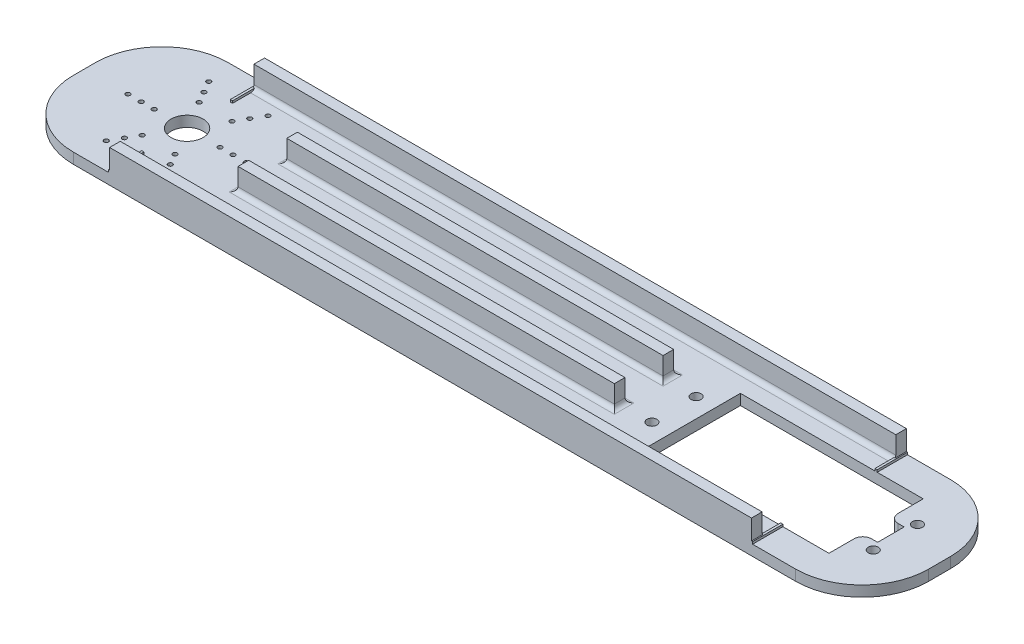
SolidWorks part; units mm, degrees
ref_plane "Front Plane" through (0, 0, 0) normal (0, 0, 1) x (1, 0, 0)
ref_plane "Top Plane" through (0, 0, 0) normal (0, 1, 0) x (1, 0, 0)
ref_plane "Right Plane" through (0, 0, 0) normal (1, 0, 0) x (0, 0, -1)
sketch "Sketch1" plane through (0, 0, 0) normal (0, 1, 0) x (1, 0, 0)
  line L1 (-65.6771, 38.9958) -> (127.5229, 38.9958)
  line L2 (-65.6771, 38.9958) -> (-65.6771, 3.9958)
  line L3 (-65.6771, 3.9958) -> (127.5229, 3.9958)
  line L4 (127.5229, 38.9958) -> (127.5229, 3.9958)
  dimension "D1" = 193.2
  dimension "D2" = 35
extrude "Boss-Extrude1" add sketch "Sketch1" along normal blind 2.4
sketch "Sketch2" plane through (0, 2.4, 0) normal (0, 1, 0) x (1, 0, 0)
  line L0 (-42.4771, 38.9958) -> (-42.4771, 2.4158) construction
  line L1 (127.5229, 38.9958) -> (-65.6771, 38.9958) construction
  line L2 (-65.6771, 21.4958) -> (127.5229, 21.4958) construction
  line L3 (-65.6771, 38.9958) -> (-65.6771, 3.9958) construction
  line L4 (127.5229, 3.9958) -> (127.5229, 38.9958) construction
  line L5 (112.5229, 38.9958) -> (112.5229, 3.9958) construction
  line L6 (-65.6771, 3.9958) -> (127.5229, 3.9958) construction
  line L7 (72.5229, 38.9958) -> (72.5229, 3.9958) construction
  line L9 (72.5229, 31.4958) -> (112.5229, 31.4958)
  line L10 (72.5229, 31.4958) -> (72.5229, 11.4958)
  line L11 (72.5229, 11.4958) -> (112.5229, 11.4958)
  line L12 (112.5229, 31.4958) -> (112.5229, 11.4958)
  circle A0 centre (67.5229, 26.4958) radius 1.13
  circle A1 centre (117.5229, 26.4958) radius 1.13
  circle A2 centre (117.5229, 16.4958) radius 1.13
  circle A3 centre (67.5229, 16.4958) radius 1.13
  circle A4 centre (-42.4771, 21.4958) radius 3.625
  circle A5 centre (-49.9071, 21.4958) radius 0.5
  circle A6 centre (-52.8421, 21.4958) radius 0.5
  circle A7 centre (-55.8471, 21.4958) radius 0.5
  circle A8 centre (-49.1621, 33.0745) radius 0.5
  circle A9 centre (-47.6596, 30.4721) radius 0.5
  circle A10 centre (-46.1921, 27.9303) radius 0.5
  circle A11 centre (-35.7921, 33.0745) radius 0.5
  circle A12 centre (-37.2946, 30.4721) radius 0.5
  circle A13 centre (-38.7621, 27.9303) radius 0.5
  circle A14 centre (-29.1071, 21.4958) radius 0.5
  circle A15 centre (-32.1121, 21.4958) radius 0.5
  circle A16 centre (-35.0471, 21.4958) radius 0.5
  circle A17 centre (-35.7921, 9.917) radius 0.5
  circle A18 centre (-37.2946, 12.5194) radius 0.5
  circle A19 centre (-38.7621, 15.0612) radius 0.5
  circle A20 centre (-49.1621, 9.917) radius 0.5
  circle A21 centre (-47.6596, 12.5194) radius 0.5
  circle A22 centre (-46.1921, 15.0612) radius 0.5
  point P24 (-42.4771, 21.4958)
  point P70 (-42.4771, 21.4958)
  dimension "D5" = 2.26
  dimension "D6" = 2.26
  dimension "D11" = 7.25
  dimension "D12" = 7.43
  dimension "D13" = 10.365
  dimension "D14" = 13.37
  dimension "D15" = 1
  dimension "D16" = 1
  dimension "D17" = 1
  dimension "D19" = 20
  dimension "D1" = 23.2
  dimension "D2" = 15
  dimension "D3" = 40
  dimension "D4" = 10
  dimension "D7" = 5
  dimension "D8" = 5
  dimension "D9" = 5
  dimension "D10" = 5
  dimension "D18" = 6
extrude "Cut-Extrude1" cut sketch "Sketch2" against normal blind 2.4
sketch "Sketch4" plane through (0, 2.4, 0) normal (0, 1, 0) x (1, 0, 0)
  line L0 (72.5229, 21.4958) -> (127.5229, 21.4958) construction
  line L1 (72.5229, 31.4958) -> (72.5229, 11.4958) construction
  line L2 (127.5229, 3.9958) -> (127.5229, 38.9958) construction
  line L3 (112.5229, 11.4958) -> (112.5229, 31.4958) construction
  line L4 (112.5229, 24.4958) -> (116.5229, 24.4958)
  line L5 (112.5229, 24.4958) -> (112.5229, 18.4958)
  line L6 (112.5229, 18.4958) -> (116.5229, 18.4958)
  line L7 (116.5229, 24.4958) -> (116.5229, 18.4958)
  dimension "D1" = 6
  dimension "D2" = 3
  dimension "D3" = 4
extrude "Cut-Extrude2" cut sketch "Sketch4" against normal blind 2.4
fillet "Fillet1" radius 15 4 edges at (127.5229, 1.2, -38.9958) (127.5229, 1.2, -3.9958) (-65.6771, 1.2, -3.9958) (-65.6771, 1.2, -38.9958)
sketch "Sketch5" plane through (0, 2.4, 0) normal (0, 1, 0) x (1, 0, 0)
  line L0 (-42.4771, 21.4958) -> (127.5229, 21.4958) construction
  line L1 (127.5229, 18.9958) -> (127.5229, 23.9958) construction
  line L2 (-42.4771, 38.9958) -> (-42.4771, 3.9958) construction
  line L3 (112.5229, 38.9958) -> (-50.6771, 38.9958) construction
  line L4 (-50.6771, 3.9958) -> (112.5229, 3.9958) construction
  line L5 (102.5229, 38.9958) -> (102.5229, 3.9958) construction
  line L6 (112.5229, 31.4958) -> (72.5229, 31.4958) construction
  line L7 (102.2729, 38.9958) -> (102.7729, 38.9958)
  line L8 (102.2729, 38.9958) -> (102.2729, 31.4958)
  line L9 (102.2729, 31.4958) -> (102.7729, 31.4958)
  line L10 (102.7729, 38.9958) -> (102.7729, 31.4958)
  line L11 (102.7729, 3.9958) -> (102.7729, 11.4958)
  line L12 (102.2729, 11.4958) -> (102.7729, 11.4958)
  line L13 (102.2729, 3.9958) -> (102.2729, 11.4958)
  line L14 (102.2729, 3.9958) -> (102.7729, 3.9958)
  line L15 (-42.2271, 3.9958) -> (-42.2271, 11.4958)
  line L16 (-42.7271, 38.9958) -> (-42.2271, 38.9958)
  line L17 (-42.7271, 38.9958) -> (-42.7271, 31.4958)
  line L18 (-42.7271, 31.4958) -> (-42.2271, 31.4958)
  line L19 (-42.2271, 38.9958) -> (-42.2271, 31.4958)
  line L20 (-42.7271, 11.4958) -> (-42.2271, 11.4958)
  line L21 (-42.7271, 3.9958) -> (-42.7271, 11.4958)
  line L22 (-42.7271, 3.9958) -> (-42.2271, 3.9958)
  dimension "D1" = 145
  dimension "D2" = 0.5
  dimension "D3" = 0.25
  dimension "D4" = 0.25
  dimension "D5" = 0.5
  dimension "D6" = 7.5
extrude "Boss-Extrude2" add sketch "Sketch5" along normal blind 0.5
sketch "Sketch7" plane through (0, 2.4, 0) normal (0, 1, 0) x (1, 0, 0)
  line L0 (71.8729, 32.1458) -> (71.8729, 10.8458)
  line L1 (72.5229, 31.4958) -> (112.5229, 31.4958)
  line L2 (72.5229, 31.4958) -> (72.5229, 11.4958)
  line L3 (72.5229, 11.4958) -> (112.5229, 11.4958)
  line L4 (112.5229, 31.4958) -> (112.5229, 11.4958)
  line L5 (71.8729, 10.8458) -> (113.1729, 10.8458)
  line L6 (113.1729, 32.1458) -> (113.1729, 10.8458)
  line L7 (71.8729, 32.1458) -> (113.1729, 32.1458)
  dimension "D1" = 0.65
extrude "Cut-Extrude3" cut sketch "Sketch7" against normal through all both and the other way through all
sketch "Sketch8" plane through (0, 2.4, 0) normal (0, 1, 0) x (1, 0, 0)
  line L0 (102.5229, 38.9958) -> (102.5229, 3.9958) construction
  line L1 (-42.4771, 38.9958) -> (102.5229, 38.9958)
  line L2 (-42.4771, 38.9958) -> (-42.4771, 36.5958)
  line L3 (-42.4771, 36.5958) -> (102.5229, 36.5958)
  line L4 (102.5229, 38.9958) -> (102.5229, 36.5958)
  line L5 (-24.2566, 3.9958) -> (-24.2566, 38.9958) construction
  line L6 (-42.2271, 3.9958) -> (102.2729, 3.9958) construction
  line L7 (-42.4771, 21.4958) -> (116.5229, 21.4958) construction
  line L8 (-24.2566, 28.1958) -> (60.7434, 28.1958)
  line L9 (-24.2566, 28.1958) -> (-24.2566, 25.7958)
  line L10 (-24.2566, 25.7958) -> (60.7434, 25.7958)
  line L11 (60.7434, 28.1958) -> (60.7434, 25.7958)
  line L12 (116.5229, 18.4958) -> (116.5229, 24.4958) construction
  line L13 (60.7434, 14.7958) -> (60.7434, 17.1958)
  line L14 (-24.2566, 17.1958) -> (60.7434, 17.1958)
  line L15 (-24.2566, 14.7958) -> (-24.2566, 17.1958)
  line L16 (-24.2566, 14.7958) -> (60.7434, 14.7958)
  line L17 (102.5229, 3.9958) -> (102.5229, 6.3958)
  line L18 (-42.4771, 6.3958) -> (102.5229, 6.3958)
  line L19 (-42.4771, 3.9958) -> (-42.4771, 6.3958)
  line L20 (-42.4771, 3.9958) -> (102.5229, 3.9958)
  dimension "D1" = 2.4
  dimension "D2" = 2.4
  dimension "D3" = 85
  dimension "D4" = 8.4
extrude "Boss-Extrude3" add sketch "Sketch8" along normal blind 5
fillet "Fillet2" radius 2 2 edges at (113.1729, 1.2, -18.4958) (113.1729, 1.2, -24.4958)
fillet "Fillet3" radius 1 10 edges at (18.2434, 2.4, -28.1958) (18.2434, 2.4, -17.1958) (30.0229, 2.4, -6.3958) (60.7434, 2.4, -15.9958) (60.7434, 2.4, -26.9958) (-24.2566, 2.4, -26.9958) (-24.2566, 2.4, -15.9958) (18.2434, 2.4, -14.7958) (18.2434, 2.4, -25.7958) (30.0229, 2.4, -36.5958)
